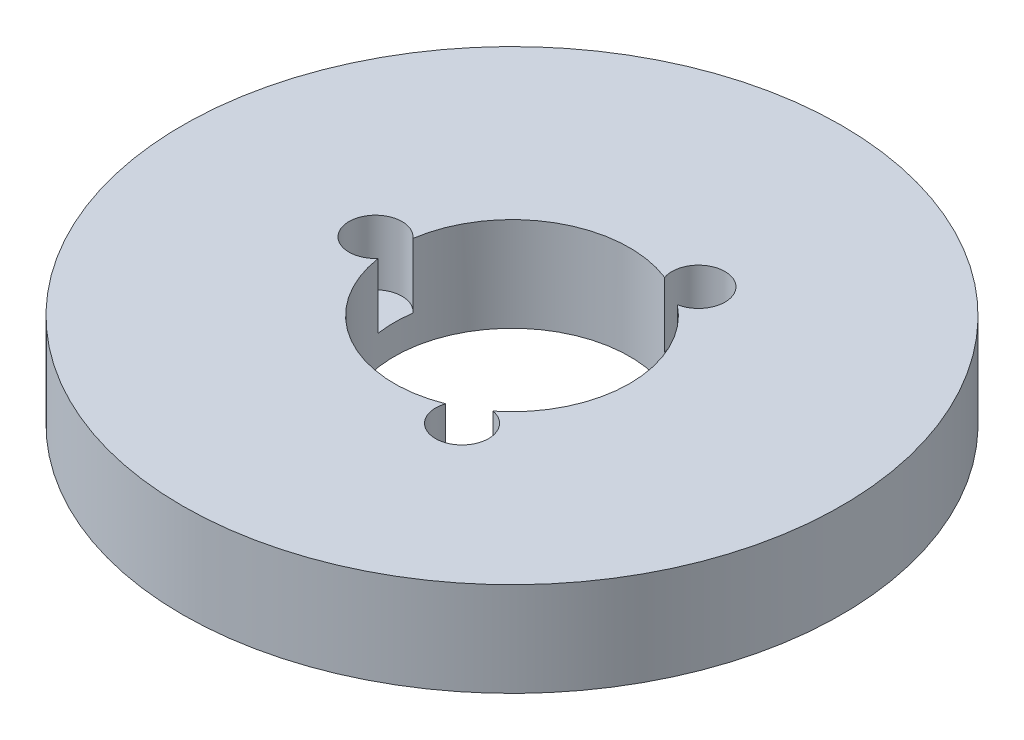
SolidWorks part; units mm, degrees
ref_plane "Front Plane" through (0, 0, 0) normal (0, 0, 1) x (1, 0, 0)
ref_plane "Top Plane" through (0, 0, 0) normal (0, 1, 0) x (1, 0, 0)
ref_plane "Right Plane" through (0, 0, 0) normal (1, 0, 0) x (0, 0, -1)
sketch "Sketch1" plane through (0, 0, 0) normal (0, 1, 0) x (1, 0, 0)
  circle A0 centre (0, 0) radius 35
  dimension "FLANGE_OD" = 70
extrude "Boss-Extrude1" add sketch "Sketch1" along normal blind 10
sketch "Sketch2" plane through (0, 0, 0) normal (0, 1, 0) x (1, 0, 0)
  circle A0 centre (0, 0) radius 12.5
  dimension "BORE_D" = 25
extrude "Cut-Extrude1" cut sketch "Sketch2" along normal through all
sketch "Sketch3" plane through (0, 10, 0) normal (0, 1, 0) x (1, 0, 0)
  circle A0 centre (0, 0) radius 14.4978 construction
  circle A1 centre (-14.4978, 0) radius 2.8193
  dimension "BOLT_D" = 5.6387
  dimension "BOLT_PCD" = 28.9956
extrude "Cut-Extrude2" cut sketch "Sketch3" against normal blind 6.8709
pattern_circular "CirPattern1" count 3 over 360 about axis through (0, 0, 0) along (0, 1, 0) of "Cut-Extrude2"
